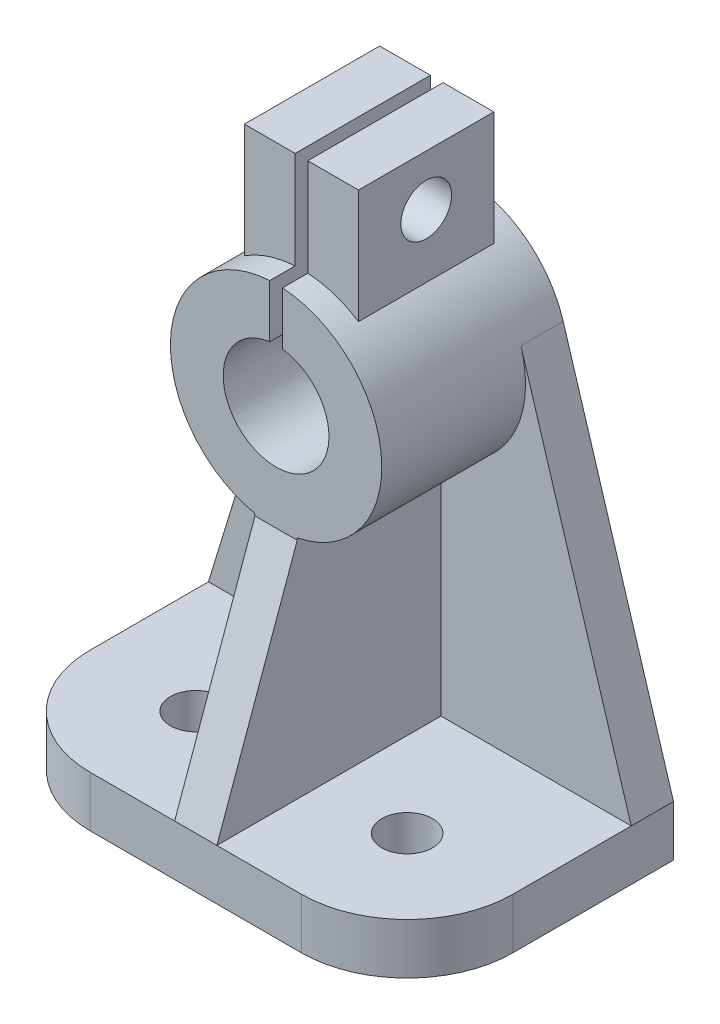
SolidWorks part; units mm, degrees
ref_plane "Front Plane" through (0, 0, 0) normal (0, 0, 1) x (1, 0, 0)
ref_plane "Top Plane" through (0, 0, 0) normal (0, 1, 0) x (1, 0, 0)
ref_plane "Right Plane" through (0, 0, 0) normal (1, 0, 0) x (0, 0, -1)
sketch "Sketch1" plane through (0, 0, 0) normal (0, 1, 0) x (1, 0, 0)
  line L1 (-50, 31.5) -> (50, 31.5)
  line L2 (-50, 31.5) -> (-50, -31.5)
  line L3 (-50, -31.5) -> (50, -31.5)
  line L4 (50, 31.5) -> (50, -31.5)
  line L5 (-50, 31.5) -> (50, -31.5) construction
  line L6 (-50, -31.5) -> (50, 31.5) construction
  point P0 (0, 0)
  dimension "D1" = 100
  dimension "D2" = 63
extrude "Boss-Extrude1" add sketch "Sketch1" along normal blind 12
fillet "Fillet1" radius 25 2 edges at (50, 6, 31.5) (-50, 6, 31.5)
sketch "Sketch2" plane through (0, 12, 0) normal (0, 1, 0) x (1, 0, 0)
  line L0 (-50, -6.5) -> (52.5652, -6.5) construction
  line L1 (-25, -33.2805) -> (-25, 38.4882) construction
  line L2 (25, -31.5) -> (25, 40.1156) construction
  circle A0 centre (-25, -6.5) radius 6
  circle A1 centre (25, -6.5) radius 6
  dimension "D1" = 12
extrude "Cut-Extrude1" cut sketch "Sketch2" against normal through all
sketch "Sketch4" plane through (0, 0, -31.5) normal (0, 0, -1) x (-1, 0, 0)
  line L0 (0, 0) -> (0, 90) construction
  line L1 (-23.9068, 97.312) -> (-50, 12)
  line L2 (-50, 12) -> (50, 12)
  line L3 (50, 12) -> (23.9068, 97.312)
  circle A0 centre (0, 90) radius 25
  point P7 (-24.6562, 94.132)
  point P11 (23.9068, 97.312)
  dimension "D1" = 50
  dimension "D2" = 90
extrude "Boss-Extrude2" add sketch "Sketch4" against normal blind 10 contours L2 L0 A0 L1 | L0 A0 L3 | A0 region at (21.4549, 40.5565, -31.5) region at (-21.4549, 40.5565, -31.5) region at (19.5288, 75.5512, -31.5)
extrude "Boss-Extrude3" add sketch "Sketch4<4>" against normal blind 44 contours A0
sketch "Sketch4<4>" plane through (0, 0, -31.5) normal (0, 0, -1) x (-1, 0, 0) same geometry as "Sketch4"
sketch "Sketch5" plane through (0, 0, 12.5) normal (0, 0, 1) x (1, 0, 0)
  circle A0 centre (0, 90) radius 12.5
  dimension "D1" = 25
extrude "Cut-Extrude2" cut sketch "Sketch5" against normal through all
ref_plane "Plane1" through (0, 138, 0) normal (0, 1, 0) x (1, 0, 0)
sketch "Sketch6" plane through (0, 138, 0) normal (0, 1, 0) x (1, 0, 0)
  line L0 (0, 0) -> (0, 47.3312) construction
  line L1 (23.9068, 31.5) -> (-23.9068, 31.5) construction
  line L2 (-13.5, 25.5) -> (13.5, 25.5)
  line L3 (-13.5, 25.5) -> (-13.5, -6.5)
  line L4 (-13.5, -6.5) -> (13.5, -6.5)
  line L5 (13.5, 25.5) -> (13.5, -6.5)
  line L6 (-13.5, 25.5) -> (13.5, -6.5) construction
  line L7 (-13.5, -6.5) -> (13.5, 25.5) construction
  point P3 (0, 9.5)
  dimension "D1" = 27
  dimension "D2" = 32
  dimension "D3" = 6
extrude "Boss-Extrude4" add sketch "Sketch6" against normal up to surface (26.9584 mm away) up to face at (0, 93.656, -26.5)
sketch "Sketch7" plane through (0, 0, 12.5) normal (0, 0, 1) x (1, 0, 0)
  line L0 (0, 0) -> (0, 153.575) construction
  line L2 (-1.5, 158.4577) -> (1.5, 158.4577)
  line L3 (-1.5, 158.4577) -> (-1.5, 96.3779)
  line L4 (-1.5, 96.3779) -> (1.5, 96.3779)
  line L5 (1.5, 158.4577) -> (1.5, 96.3779)
  line L6 (-1.5, 158.4577) -> (1.5, 96.3779) construction
  line L7 (-1.5, 96.3779) -> (1.5, 158.4577) construction
  point P3 (0, 127.4178)
  dimension "D1" = 3
extrude "Cut-Extrude3" cut sketch "Sketch7" against normal blind 44
sketch "Sketch8" plane through (-13.5, 0, 0) normal (-1, 0, 0) x (0, 0, 1)
  line L0 (-9.5, 111.0416) -> (-9.5, 141.8043) construction
  line L1 (6.5, 111.0416) -> (-25.5, 111.0416) construction
  line L3 (-9.5, 126) -> (-29.6395, 126) construction
  line L4 (-25.5, 138) -> (6.5, 138) construction
  circle A0 centre (-9.5, 126) radius 6
  dimension "D1" = 12
  dimension "D2" = 12
extrude "Cut-Extrude4" cut sketch "Sketch8" against normal through all
sketch "Sketch9" plane through (0, 0, 0) normal (1, 0, 0) x (0, 0, -1)
  line L0 (-31.5, 12) -> (21.5, 12)
  line L1 (21.5, 12) -> (21.5, 65)
  line L2 (21.5, 65) -> (-12.5, 65)
  line L3 (-12.5, 65) -> (-31.5, 12)
extrude "Boss-Extrude6" add sketch "Sketch9" along normal mid plane 10 separate body
sketch "Sketch10" plane through (0, 65, 0) normal (0, 1, 0) x (1, 0, 0)
  line L4 (-5, 21.5) -> (-5, -12.5)
  line L5 (-5, -12.5) -> (5, -12.5)
  line L6 (5, -12.5) -> (5, 21.5)
  line L7 (5, 21.5) -> (-5, 21.5)
  line L8 (-5, 21.5) -> (-5, -12.5)
  line L9 (-5, -12.5) -> (5, -12.5)
  line L10 (5, -12.5) -> (5, 21.5)
  line L11 (5, 21.5) -> (-5, 21.5)
  dimension "D1" = 0
extrude "Boss-Extrude7" add sketch "Sketch10" along normal up to surface up to face at (0, 105.0552, -13.75)
